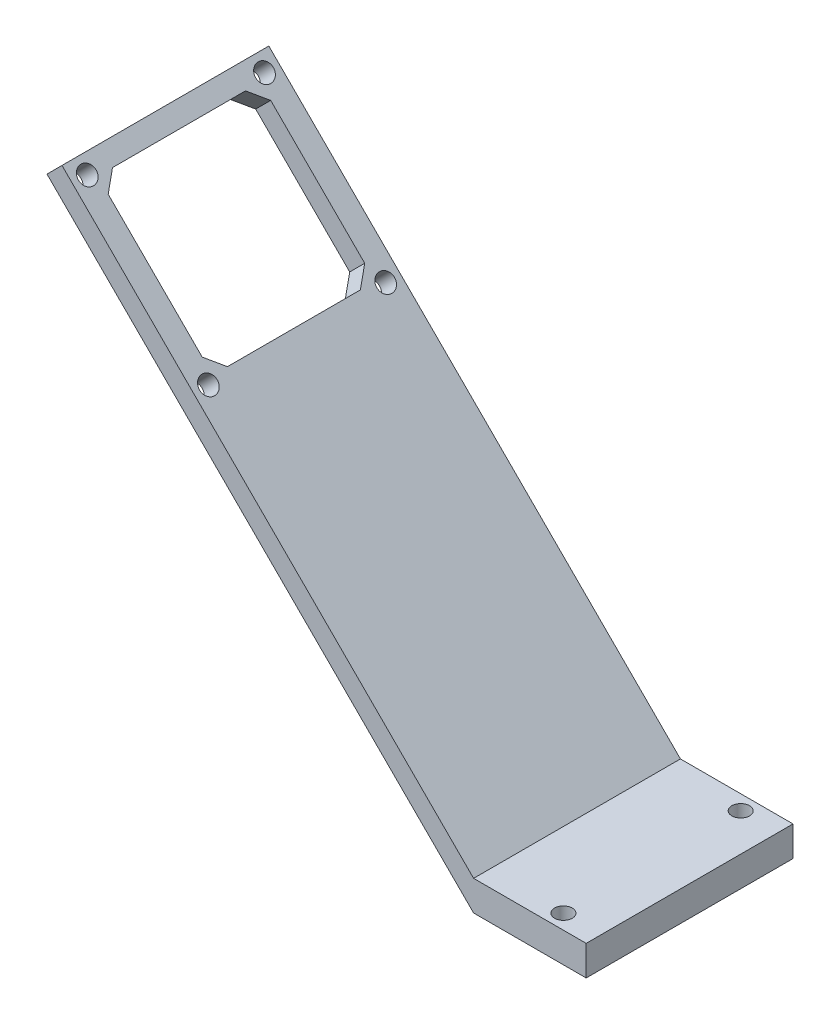
SolidWorks part; units mm, degrees
ref_plane "Front Plane" through (0, 0, 0) normal (0, 0, 1) x (1, 0, 0)
ref_plane "Top Plane" through (0, 0, 0) normal (0, 1, 0) x (1, 0, 0)
ref_plane "Right Plane" through (0, 0, 0) normal (1, 0, 0) x (0, 0, -1)
sketch "Sketch2" plane through (0, 0, 0) normal (0, 0, 1) x (1, 0, 0)
  line L0 (-47.4413, 42.3613) -> (0, -5.08)
  line L1 (19.05, -5.08) -> (0, -5.08)
  line L2 (19.05, -5.08) -> (19.05, 0)
  line L3 (19.05, 0) -> (0, 0)
  line L4 (0, -5.08) -> (0, 0)
  line L5 (-47.4413, 42.3613) -> (-44.9013, 44.9013)
  line L6 (-44.9013, 44.9013) -> (0, 0)
  line L7 (-47.4413, 42.3613) -> (-44.9013, 44.9013)
  line L8 (-47.4413, 42.3613) -> (-72.19, 67.11)
  line L9 (-44.9013, 44.9013) -> (-69.65, 69.65)
  line L10 (-72.19, 67.11) -> (-69.65, 69.65)
  dimension "D2" = 5.08
  dimension "D3" = 19.05
  dimension "D4" = 63.5
  dimension "D5" = 35
  dimension "60" = 45
extrude "Boss-Extrude1" add sketch "Sketch2" along normal blind 35 contours L10 L8 L5 L9 | L6 L5 L0 L4 | L4 L1 L2 L3 region at (-23.0915, 20.5282, 0) region at (-58.5456, 56.0056, 0) region at (9.525, -2.54, 0)
sketch "Sketch3" plane through (0, 0, 0) normal (0.7071, 0.7071, 0) x (0.7071, -0.7071, 0)
  line L0 (0, 0) -> (-98.5, 0) construction
  line L1 (-96, -2.5) -> (-67, -2.5) construction
  line L2 (-96, -2.5) -> (-96, -32.5) construction
  line L3 (-96, -32.5) -> (-67, -32.5) construction
  line L4 (-67, -2.5) -> (-67, -32.5) construction
  line L5 (-98.5, -35) -> (-98.5, 0) construction
  line L6 (-94, -17.5) -> (-69, -17.5) construction
  line L7 (-94, -5) -> (-69, -5)
  line L8 (-94, -5) -> (-94, -30)
  line L9 (-94, -30) -> (-69, -30)
  line L10 (-69, -5) -> (-69, -30)
  line L11 (-94, -5) -> (-69, -5)
  line L12 (-94, -5) -> (-94, -3.75)
  line L13 (-94, -3.75) -> (-69, -3.75)
  line L14 (-69, -5) -> (-69, -3.75)
  line L15 (-69, -30) -> (-69, -31.25)
  line L16 (-94, -31.25) -> (-69, -31.25)
  line L17 (-94, -30) -> (-94, -31.25)
  line L18 (-81.5, -5) -> (-81.5, -30) construction
  line L19 (-94, -5) -> (-95.25, -5)
  line L20 (-94, -5) -> (-94, -30)
  line L21 (-94, -30) -> (-95.25, -30)
  line L22 (-95.25, -5) -> (-95.25, -30)
  line L23 (-69, -5) -> (-67.75, -5)
  line L24 (-69, -30) -> (-67.75, -30)
  line L25 (-67.75, -5) -> (-67.75, -30)
  line L26 (-70.25, -3.75) -> (-67.75, -6.25)
  line L27 (-70.25, -31.25) -> (-67.75, -28.75)
  line L28 (-92.75, -3.75) -> (-95.25, -6.25)
  line L29 (-92.75, -31.25) -> (-95.25, -28.75)
  point P16 (-81.5, -3.75)
  point P17 (-81.5, -5)
  point P30 (-96, -17.5)
  point P32 (-81.5, -2.5)
  dimension "D1" = 2.5
  dimension "D2" = 29
  dimension "D3" = 2.5
  dimension "D4" = 30
  dimension "D6" = 25
  dimension "D7" = 1.25
  dimension "D8" = 25
  dimension "D9" = 1.25
extrude "Cut-Extrude1" cut sketch "Sketch3" against normal through all contours L10 L7 L8 L9 | L13 L28 L7 L26 | L29 L8 L28 L22 | L10 L27 L25 L26 | L29 L16 L27 L9 region at (-57.6292, 57.6292, 4.386) region at (-57.6292, 57.6292, 17.5) region at (-66.9022, 66.9022, 17.5) region at (-48.3562, 48.3562, 17.5) region at (-57.6292, 57.6292, 30.614)
hole_wizard "Ø3.0mm Dowel Hole1" positions "3DSketch1" profile "Sketch4" hole size "Ø3.0" standard "ANSI Metric" end condition through all
sketch3d "3DSketch1"
  point P0 (-67.8823, 67.8823, 2.5)
  point P3 (-47.3762, 47.3762, 2.5)
  point P6 (-47.3762, 47.3762, 32.5)
  point P9 (-67.8823, 67.8823, 32.5)
sketch "Sketch4" plane through (-67.8823, 67.8823, 2.5) normal (0, 0, 1) x (-0.7071, 0.7071, 0)
  line L0 (0, 0) -> (0, 54.6382)
  line L1 (0, 54.6382) -> (1.5, 54.6382)
  line L2 (1.5, 54.6382) -> (1.5, 0)
  line L5 (1.5, 0) -> (0, 0)
  line L11 (0, -6.35) -> (0, 107.95) construction
  dimension "Thru Hole Dia." = 3
  dimension "Thru Hole Depth" = 54.6382
sketch "Sketch5" plane through (0, 0, 0) normal (0, 1, 0) x (1, 0, 0)
  line L0 (19.05, -35) -> (19.05, 0) construction
  line L1 (19.05, -2.5) -> (12.7, -2.5)
  line L2 (19.05, -2.5) -> (19.05, -32.5)
  line L3 (19.05, -32.5) -> (12.7, -32.5)
  line L4 (12.7, -2.5) -> (12.7, -32.5)
  point P6 (19.05, -17.5)
  dimension "D1" = 6.35
  dimension "D2" = 30
  dimension "D3" = 17.5
hole_wizard "Ø3.0mm Dowel Hole2" positions "3DSketch2" profile "Sketch6" hole size "Ø3.0" standard "ANSI Metric" end condition through all
sketch3d "3DSketch2"
  point P0 (12.7, 0, 2.5)
  point P3 (12.7, 0, 32.5)
sketch "Sketch6" plane through (12.7, 0, 2.5) normal (1, 0, 0) x (0, 0, 1)
  line L0 (0, 0) -> (0, 5.08)
  line L1 (0, 5.08) -> (1.5, 5.08)
  line L2 (1.5, 5.08) -> (1.5, 0)
  line L5 (1.5, 0) -> (0, 0)
  line L11 (0, -6.35) -> (0, 107.95) construction
  dimension "Thru Hole Dia." = 3
  dimension "Thru Hole Depth" = 5.08
